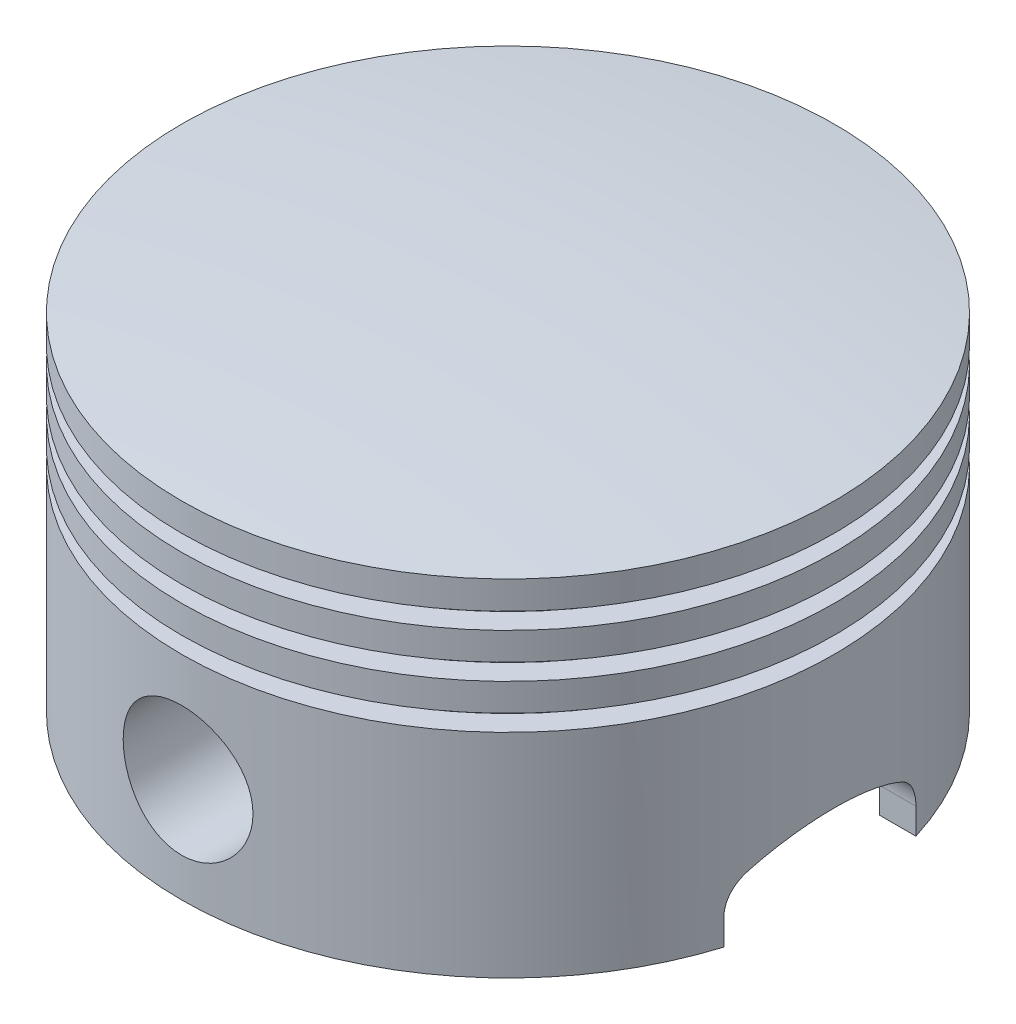
SolidWorks part; units mm, degrees
ref_plane "Front Plane" through (0, 0, 0) normal (0, 0, 1) x (1, 0, 0)
ref_plane "Top Plane" through (0, 0, 0) normal (0, 1, 0) x (1, 0, 0)
ref_plane "Right Plane" through (0, 0, 0) normal (1, 0, 0) x (0, 0, -1)
sketch "Sketch1" plane through (0, 0, 0) normal (0, 1, 0) x (1, 0, 0)
  circle A0 centre (0, 0) radius 85
extrude "Boss-Extrude3" add sketch "Sketch1" against normal blind 90
sketch "Sketch4" plane through (0, 0, 0) normal (0, 1, 0) x (1, 0, 0)
  circle A0 centre (0, 0) radius 79
extrude "Cut-Extrude3" cut sketch "Sketch4" against normal blind 4.3 from offset 7.3 flip side to cut offset against normal yes
pattern_linear "LPattern1" count 3 spacing 11.5 along (0, -1, 0) of "Cut-Extrude3"
sketch "Sketch5" plane through (0, -90, 0) normal (0, -1, 0) x (1, 0, 0)
  circle A0 centre (0, 0) radius 76
extrude "Cut-Extrude4" cut sketch "Sketch5" against normal blind 85
dome "Dome1" faces to dome 1 distance 5 reverse direction no elliptical dome no face at (0, 0, 85) parameters "D1"=5
sketch "Sketch6" plane through (0, 0, 0) normal (0, 0, 1) x (1, 0, 0)
  circle A0 centre (0, -62.6052) radius 33.8
sketch "Sketch7" plane through (0, 0, 0) normal (0, 0, 1) x (1, 0, 0)
  line L0 (-85, -90) -> (85, -90) construction
  circle A0 centre (0, -63) radius 16.9
  dimension "D1" = 27
  dimension "D2" = 33.8
extrude "Cut-Extrude5" cut sketch "Sketch7" against normal through all both and the other way through all contours A0
sketch "Sketch8" plane through (0, 0, 0) normal (1, 0, 0) x (0, 0, -1)
  line L0 (0, -90) -> (0, -61.8849)
  line L1 (-85, -90) -> (85, -90) construction
  line L2 (-25, -90) -> (-25, -78)
  line L3 (25, -90) -> (25, -78)
  line L4 (-25, -90) -> (25, -90)
  arc A0 (-25, -78) -> (25, -78) centre (0, -109.225) cw
  dimension "D1" = 12
  dimension "D3" = 40
  dimension "D2" = 50
extrude "Cut-Extrude6" cut sketch "Sketch8" against normal through all both and the other way through all contours A0 L3 L4 L2
fillet "Fillet1" radius 10 4 edges at (76.5054, -78, -25) (-76.5054, -78, -25) (-76.5054, -78, 25) (76.5054, -78, 25)
sketch "Sketch9" plane through (0, 0, 0) normal (0, 0, 1) x (1, 0, 0)
  circle A0 centre (0, -63) radius 16.9 construction
  circle A1 centre (0, -63) radius 16.9
  circle A2 centre (0, -63) radius 22.5
extrude "Boss-Extrude4" add sketch "Sketch9" along normal up to next from offset 19
mirror "Mirror1" about plane through (0, 0, 0) normal (0, 0, 1) of "Cut-Extrude5"
mirror "Mirror2" about plane through (0, 0, 0) normal (0, 0, 1) of "Cut-Extrude5"
mirror "Mirror3" about plane through (0, 0, 0) normal (0, 0, 1) of "Cut-Extrude5", "Boss-Extrude4"
